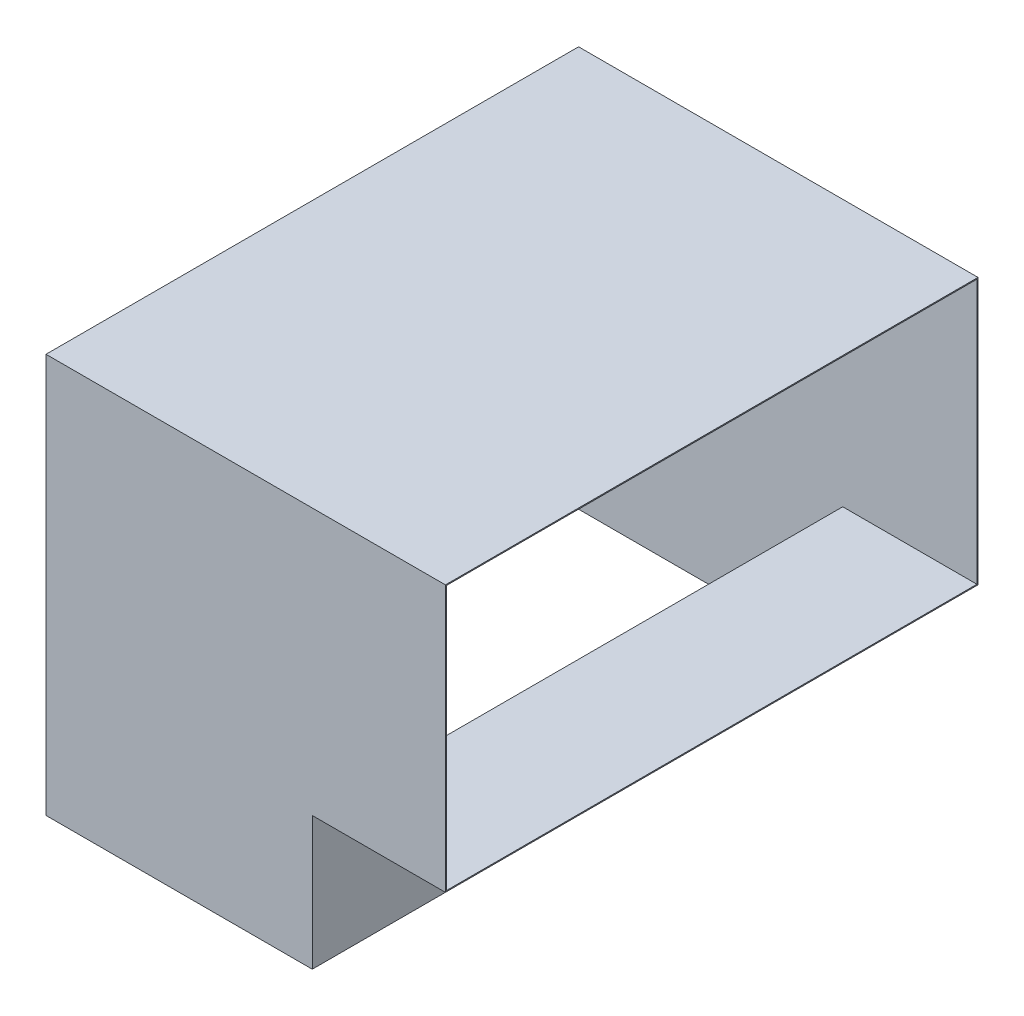
SolidWorks part; units mm, degrees
material "Plain Carbon Steel"
ref_plane "Front Plane" through (0, 0, 0) normal (0, 0, 1) x (1, 0, 0)
ref_plane "Top Plane" through (0, 0, 0) normal (0, 1, 0) x (1, 0, 0)
ref_plane "Right Plane" through (0, 0, 0) normal (1, 0, 0) x (0, 0, -1)
sketch "Sketch1" plane through (0, 0, 0) normal (1, 0, 0) x (0, 0, -1)
  line L0 (-500, 250) -> (500, -250) construction
  line L1 (-500, 250) -> (500, 250)
  line L2 (-500, 250) -> (-500, -250)
  line L3 (-500, -250) -> (500, -250)
  line L4 (500, 250) -> (500, -250)
  dimension "Width" = 1000
  dimension "Height" = 500
extrude "Extrude-Thin1" add sketch "Sketch1" along normal blind 500 and the other way blind 250 thin thin type one direction reverse wall 2
sketch "Sketch2" plane through (0, -250, 0) normal (0, -1, 0) x (1, 0, 0)
  line L1 (-250, 500) -> (250, 500)
  line L2 (-250, 500) -> (-250, -500)
  line L3 (-250, -500) -> (250, -500)
  line L4 (250, 500) -> (250, -500)
  line L6 (-250, 500) -> (250, -500) construction
  dimension "Height" = 500
  dimension "Width" = 1000
extrude "Extrude-Thin2" add sketch "Sketch2" along normal blind 250 and the other way up to next (500 mm away) thin thin type one direction reverse wall 2
sketch "Sketch3" plane through (0, -500, 0) normal (0, -1, 0) x (1, 0, 0)
  line L0 (-248, 498) -> (-248, -498) construction
  line L1 (248, 498) -> (-248, 498) construction
  line L2 (248, -498) -> (248, 498) construction
  line L3 (-248, -498) -> (248, -498) construction
  line L4 (-248, 498) -> (-248, -498)
  line L5 (248, 498) -> (-248, 498)
  line L6 (248, -498) -> (248, 498)
  line L7 (-248, -498) -> (248, -498)
extrude "Cut-Extrude1" cut sketch "Sketch3" against normal up to next
sketch "Sketch4" plane through (500, 0, 0) normal (1, 0, 0) x (0, 0, -1)
  line L0 (498, 248) -> (-498, 248) construction
  line L1 (498, -248) -> (498, 248) construction
  line L2 (-498, -248) -> (498, -248) construction
  line L3 (-498, 248) -> (-498, -248) construction
  line L4 (498, 248) -> (-498, 248)
  line L5 (498, -248) -> (498, 248)
  line L6 (-498, -248) -> (498, -248)
  line L7 (-498, 248) -> (-498, -248)
extrude "Cut-Extrude2" cut sketch "Sketch4" against normal up to next
sketch "Sketch5" plane through (0, 0, 0) normal (0, 0, 1) x (1, 0, 0)
  line L0 (500, -248) -> (500, 248) construction
  line L1 (-250, -248) -> (-250, 248) construction
  line L2 (250, -500) -> (-250, -500) construction
  point P0 (500, 0)
  point P1 (0, 0)
  point P2 (-250, 0)
  point P4 (0, -500)
other "CPoint1" parameters "Diameter"=564.1896, "StubLength"=500
ref_axis "Axis1" through (510, 0, 0) along (-1, 0, 0)
other "CPoint2" parameters "Diameter"=564.1896, "StubLength"=500
ref_axis "Axis3" through (0, -510, 0) along (0, 1, 0)
other "RPoint1"
equation "\"D1@Extrude-Thin2\"=0.5*\"Height@Sketch1\""
equation "\"D5@Extrude-Thin2\"=\"Thickness@Extrude-Thin1\""
equation "\"D1@Extrude-Thin1\"=\"Height@Sketch1\""
equation "\"D2@Extrude-Thin1\"=0.5*\"Height@Sketch1\""
